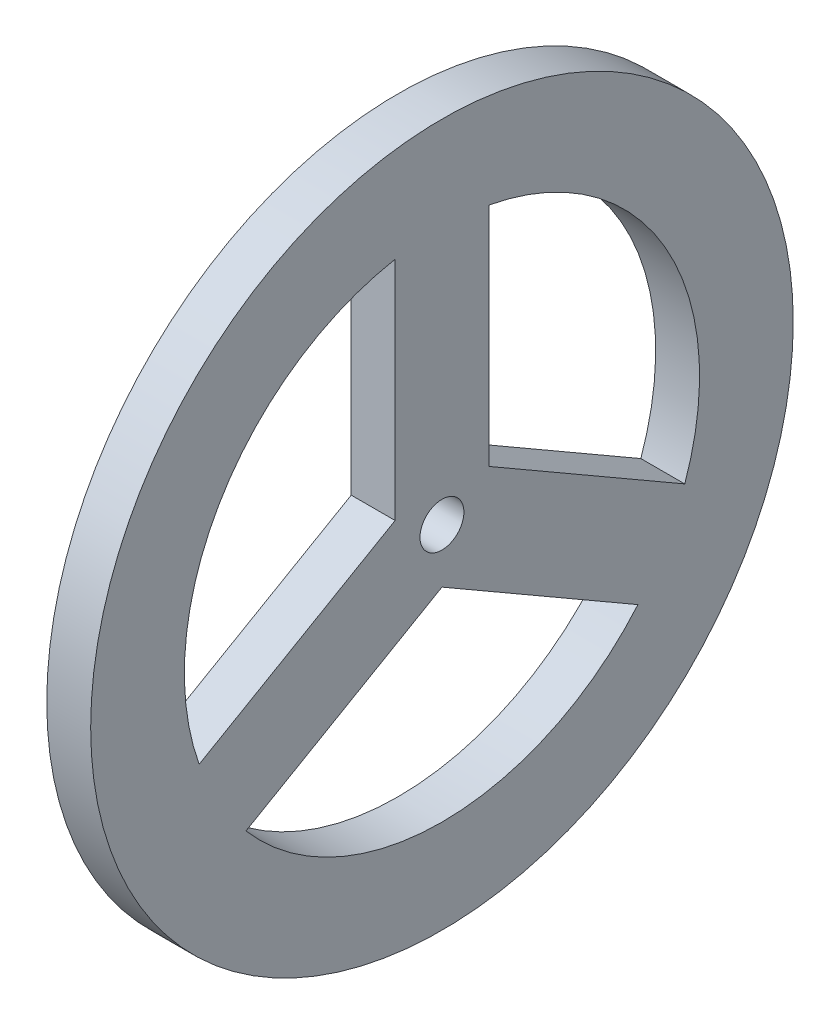
SolidWorks part; units mm, degrees
material "Corrugated Paper"
ref_plane "Front Plane" through (0, 0, 0) normal (0, 0, 1) x (1, 0, 0)
ref_plane "Top Plane" through (0, 0, 0) normal (0, 1, 0) x (1, 0, 0)
ref_plane "Right Plane" through (0, 0, 0) normal (1, 0, 0) x (0, 0, -1)
sketch "Sketch2" plane through (0, 0, 0) normal (1, 0, 0) x (0, 0, -1)
  line L0 (0, 27.94) -> (0, 0) construction
  line L1 (0, 0) -> (24.1967, -13.97) construction
  line L2 (0, 0) -> (-24.1967, -13.97) construction
  line L3 (-2.54, -4.3994) -> (21.6567, -18.3694)
  line L4 (-2.54, 4.3994) -> (-26.7367, -9.5706)
  line L5 (-5.08, 27.94) -> (-5.08, 0)
  line L6 (2.54, 4.3994) -> (26.7367, -9.5706)
  line L7 (2.54, -4.3994) -> (-21.6567, -18.3694)
  line L8 (5.08, 27.94) -> (5.08, 0)
  circle A0 centre (0, 0) radius 38.1
  circle A1 centre (0, 0) radius 27.94
  circle A2 centre (0, 0) radius 5.08
  circle A3 centre (0, 0) radius 2.3813
  dimension "D1" = 76.2
  dimension "D3" = 10.16
  dimension "D4" = 4.7625
  dimension "D5" = 120
  dimension "D6" = 120
  dimension "D2" = 10.16
  dimension "D7" = 5.08
  dimension "D8" = 5.08
extrude "Boss-Extrude5" add sketch "Sketch2" along normal blind 4.7625 contours A0
extrude "Cut-Extrude3" cut sketch "Sketch2<3>" along direction (1, 0, 0) on the side of the normal through all contours L7 A1 L3 | L5 A1 L4 | L6 A1 L8 | A3 region at (0, -18.2942, 0) region at (0, 9.1471, 15.8433) region at (0, 9.1471, -15.8433) region at (0, 0, 0)
sketch "Sketch2<3>" plane through (0, 0, 0) normal (1, 0, 0) x (0, 0, -1) same geometry as "Sketch2"
equation "\"rodThick\"= 3/16in"
equation "\"thick\"= 3/16in"
equation "\"D1@Boss-Extrude5\"=\"thick\""
equation "\"D4@Sketch2\"=\"rodThick\""
